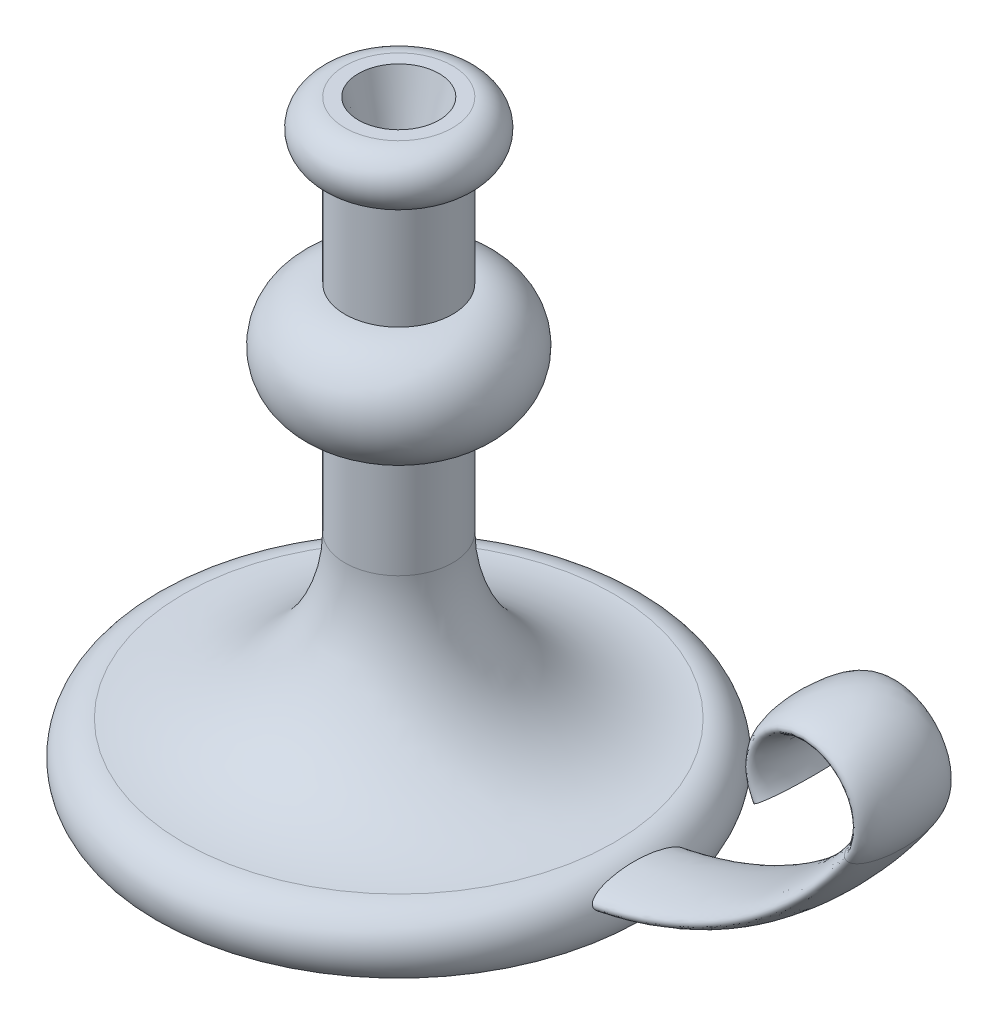
SolidWorks part; units mm, degrees
ref_plane "Front" through (0, 0, 0) normal (0, 0, 1) x (1, 0, 0)
ref_plane "Top" through (0, 0, 0) normal (0, 1, 0) x (1, 0, 0)
ref_plane "Right" through (0, 0, 0) normal (1, 0, 0) x (0, 0, -1)
sketch "Sketch1" plane through (0, 0, 0) normal (0, 0, 1) x (1, 0, 0)
  line L0 (20, 68.5) -> (0, 68.5)
  line L1 (0, 68.5) -> (0, -151.5)
  line L2 (0, -151.5) -> (90, -151.5)
  line L3 (20, -71.5) -> (20, -31.5)
  line L4 (20, 8.5) -> (20, 48.5)
  arc A0 (90, -151.5) -> (80, -131.5) centre (80, -144) ccw
  arc A1 (80, -131.5) -> (20, -71.5) centre (80, -71.5) cw
  arc A2 (20, -31.5) -> (20, 8.5) centre (20, -11.5) ccw
  arc A3 (20, 48.5) -> (20, 68.5) centre (20, 58.5) ccw
  point P13 (0, 0)
  point P15 (0, 0)
  point P16 (0, 0)
  point P17 (0, 0)
  point P18 (0, 0)
  point P19 (0, 0)
  point P20 (0, 0)
  point P21 (0, 0)
  point P22 (0, 0)
  dimension "D4" = 60
  dimension "D5" = 12.5
  dimension "D7" = 20
  dimension "D9" = 10
  dimension "D1" = 20
  dimension "D2" = 220
  dimension "D3" = 80
  dimension "D6" = 90
  dimension "D8" = 40
revolve "Revolve1" add sketch "Sketch1" angle 360 about L1
ref_axis "Axis1" through (0, -245.7184, 0) along (0, 1, 0)
ref_axis "Axis2" through (0, 8.5, 0) along (0, 1, 0)
sketch "Sketch2" plane through (0, 0, 0) normal (0, 0, 1) x (1, 0, 0)
  line L0 (0, -141.5) -> (60, -141.5)
  line L1 (0, -245.7184) -> (0, 114.0192) construction
  line L2 (-90, -151.5) -> (90, -151.5) construction
  arc A0 (60, -141.5) -> (183.5921, -76.5) centre (60, 8.5) ccw
  arc A1 (183.5921, -76.5) -> (149.8779, -75.3129) centre (167.1131, -65.1667) ccw
  point P8 (0, 0)
  point P9 (0, 0)
  point P12 (0, 0)
  point P13 (0, 0)
  point P14 (0, 0)
  dimension "D3" = 150
  dimension "D4" = 20
  dimension "D1" = 60
  dimension "D2" = 65
  dimension "D5" = 10
sketch "Sketch3" plane through (0, 0, 0) normal (1, 0, 0) x (0, 0, -1)
  ellipse E0 centre (0, -141.5) end of major axis (17.5, -141.5) minor radius 5
  point P1 (0, 0)
  point P7 (0, 0)
  point P9 (0, 0)
  point P10 (0, 0)
  dimension "D1" = 35
  dimension "D2" = 10
sweep "Sweep1" add profiles "Sketch3" path "Sketch2"
sketch "Sketch4" plane through (0, 68.5, 0) normal (0, 1, 0) x (1, 0, 0)
  circle A0 centre (0, 0) radius 15
  dimension "D1" = 30
extrude "Cut-Extrude1" cut sketch "Sketch4" against normal blind 25 draft 15
